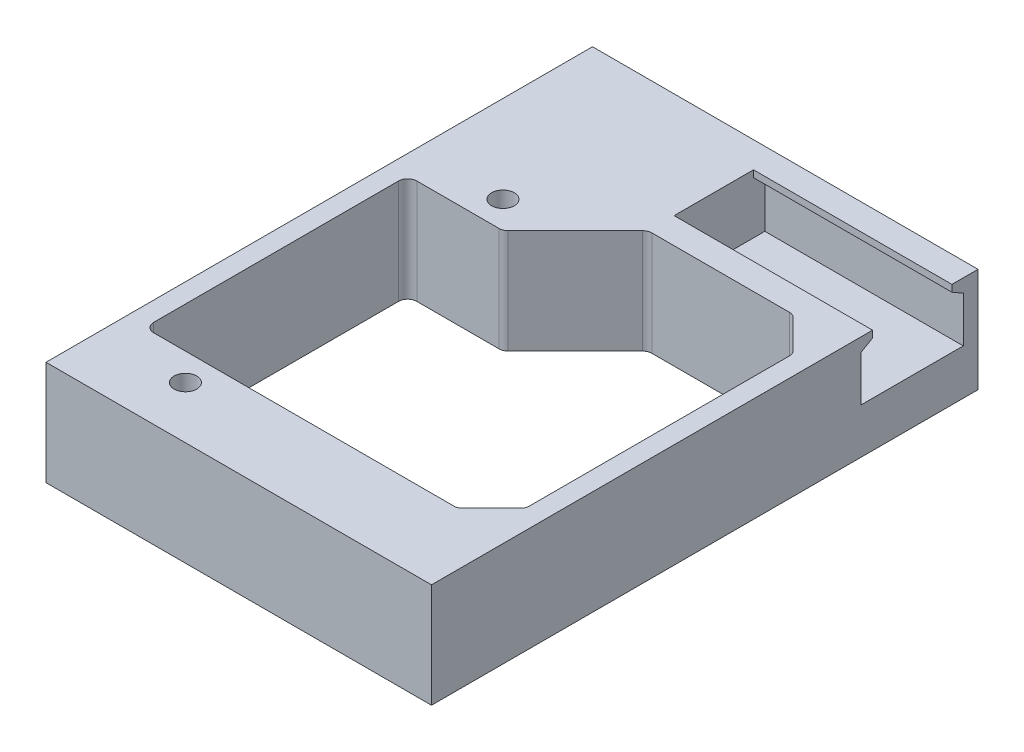
SolidWorks part; units mm, degrees
ref_plane "Front Plane" through (0, 0, 0) normal (0, 0, 1) x (1, 0, 0)
ref_plane "Top Plane" through (0, 0, 0) normal (0, 1, 0) x (1, 0, 0)
ref_plane "Right Plane" through (0, 0, 0) normal (1, 0, 0) x (0, 0, -1)
sketch "Sketch1" plane through (0, 0, 0) normal (0, 1, 0) x (1, 0, 0)
  line L0 (0, 0) -> (0, 59.6401) construction
  line L1 (-20, -19.2885) -> (-21.7, -19.2885)
  line L2 (20, 17.7115) -> (21.7, 17.7115)
  line L3 (20, 17.7115) -> (20, 69.9115)
  line L4 (20, 69.9115) -> (21.7, 69.9115)
  line L5 (21.7, 17.7115) -> (21.7, 69.9115)
  line L6 (20, 17.7115) -> (21.7, 17.7115)
  line L7 (20, 17.7115) -> (20, -19.2885)
  line L8 (20, -19.2885) -> (21.7, -19.2885)
  line L9 (21.7, 17.7115) -> (21.7, -19.2885)
  line L10 (-21.7, 17.7115) -> (-21.7, -19.2885)
  line L11 (-20, 17.7115) -> (-21.7, 17.7115)
  line L12 (-20, 17.7115) -> (-20, -19.2885)
  line L13 (-20, 69.9115) -> (-21.7, 69.9115)
  line L14 (-21.7, 17.7115) -> (-21.7, 69.9115)
  line L15 (-20, 17.7115) -> (-21.7, 17.7115)
  line L16 (-20, 17.7115) -> (-20, 69.9115)
  dimension "18" = 20
  dimension "D2" = 1.7
  dimension "D3" = 37
  dimension "D4" = 52.2
extrude "Boss-Extrude1" add sketch "Sketch1" against normal blind 9.2 from offset 1 contours L12 L11 L10 L1 | L11 L16 L13 L14 | L3 L2 L5 L4 offset against normal yes
sketch "Sketch4" plane through (0, -10.2, 0) normal (0, -1, 0) x (1, 0, 0)
  line L0 (-21.7, -69.9115) -> (-21.7, 19.2885) construction
  line L1 (12, -69.9115) -> (-21.7, -69.9115)
  line L2 (12, -69.9115) -> (12, -58.3115)
  line L3 (12, -58.3115) -> (-21.7, -58.3115)
  line L4 (-21.7, -69.9115) -> (-21.7, -58.3115)
  line L10 (-20, -69.9115) -> (-20, 19.2885) construction
  line L13 (-20, -69.9115) -> (-21.7, -69.9115) construction
  dimension "D1" = 11.6
  dimension "D2" = 32
extrude "Boss-Extrude3" add sketch "Sketch4" against normal up to surface (9.2 mm away)
sketch "Sketch3" plane through (0, -10.2, 0) normal (0, -1, 0) x (1, 0, 0)
  line L0 (-21.7, -69.9115) -> (-21.7, 19.2885) construction
  line L1 (-21.7, -58.9115) -> (-7.7, -58.9115)
  line L2 (-21.7, -58.9115) -> (-21.7, -51.9115)
  line L3 (-21.7, -51.9115) -> (-7.7, -51.9115)
  line L4 (-7.7, -58.9115) -> (-7.7, -51.9115)
  line L6 (0, 0) -> (0, -31.4212) construction
  line L13 (12, -69.9115) -> (-21.7, -69.9115) construction
  line L14 (-21.7, -40.3115) -> (-3.8096, -40.3115) construction
  line L15 (-21.7, -28.7115) -> (-7.7, -28.7115)
  line L16 (-7.7, -21.7115) -> (-7.7, -28.7115)
  line L17 (-21.7, -21.7115) -> (-7.7, -21.7115)
  line L18 (-21.7, -21.7115) -> (-21.7, -28.7115)
  line L19 (-20, -58.3115) -> (-20, 19.2885) construction
  circle A0 centre (-14, -54.3115) radius 1
  circle A2 centre (-14, -26.3115) radius 1
  dimension "D4" = 2.4
  dimension "D5" = 2
  dimension "D1" = 14
  dimension "D2" = 15.6
  dimension "D3" = 7
  dimension "D6" = 6
  dimension "D7" = 14
extrude "Servo Holder" add sketch "Sketch3" along normal blind 1 and the other way offset from surface (9.2 mm away) 1 other way up to plane "Top Plane"
sketch "Sketch37" plane through (0, -1, 0) normal (0, 1, 0) x (1, 0, 0)
  line L0 (-7.7, 21.7115) -> (-20, 21.7115) construction
  line L1 (12.3, 21.7115) -> (-7.7, 21.7115)
  line L2 (12.3, 21.7115) -> (12.3, 28.7115)
  line L3 (12.3, 28.7115) -> (-7.7, 28.7115)
  line L4 (-7.7, 21.7115) -> (-7.7, 28.7115)
  line L5 (-21.7, 69.9115) -> (-21.7, -19.2885) construction
  dimension "D1" = 34
extrude "Boss-Extrude19" add sketch "Sketch37" against normal up to surface (10.2 mm away) up to face at (-14.7, -11.2, -25.2115)
sketch "Sketch29" plane through (0, 0, -69.9115) normal (0, 0, -1) x (-1, 0, 0)
  line L1 (21.7, -10.2) -> (-12.7099, -10.2)
  line L2 (21.7, -10.2) -> (21.7, -16.1774)
  line L3 (21.7, -16.1774) -> (-12.7099, -16.1774)
  line L4 (-12.7099, -10.2) -> (-12.7099, -16.1774)
extrude "Cut-Extrude10" cut sketch "Sketch29" against normal through all both and the other way through all
sketch "Sketch30" plane through (0, 0, 0) normal (0, 0, 1) x (1, 0, 0)
  line L0 (-4.7, -1) -> (-4.7, -39) construction
  line L1 (12.3, -1) -> (-21.7, -1)
  line L2 (12.3, -1) -> (12.3, -39)
  line L3 (12.3, -39) -> (-21.7, -39)
  line L4 (-21.7, -1) -> (-21.7, -39)
  line L7 (-21.7, -1) -> (12.3, -1) construction
  line L9 (12.3, -1) -> (-20, -1) construction
  line L11 (-21.7, -10.2) -> (-21.7, -1) construction
  circle A0 centre (5.3, -34) radius 1.6
  circle A1 centre (5.3, -19) radius 1.6
  circle A2 centre (-14.7, -34) radius 1.6
  circle A3 centre (-14.7, -19) radius 1.6
  dimension "D2" = 10
  dimension "D4" = 15
  dimension "D1" = 17
  dimension "D3" = 38
  dimension "D5" = 18
  dimension "D6" = 10
extrude "Boss-Extrude13" add sketch "Sketch30" along normal blind 6.5 from offset 2 separate body
sketch "Sketch41" plane through (-20, 0, 0) normal (1, 0, 0) x (0, 0, -1)
  line L0 (21.7115, -1) -> (-19.2885, -1) construction
  line L1 (-2, -1) -> (-19.2885, -1)
  line L2 (-2, -1) -> (-2, -10.2)
  line L3 (-2, -10.2) -> (-19.2885, -10.2)
  line L4 (-19.2885, -1) -> (-19.2885, -10.2)
  line L5 (-2, -1) -> (-2, -39) construction
extrude "Cut-Extrude14" cut sketch "Sketch41" against normal blind 15
sketch "Sketch32" plane through (0, -39, 0) normal (0, -1, 0) x (1, 0, 0)
  line L1 (22.55, 8.5) -> (12.9564, 0.4867) construction
  line L2 (22.55, 8.5) -> (12.3, 8.5) construction
  line L4 (-21.7, 8.5) -> (12.3, 8.5) construction
  circle A0 centre (22.55, 8.5) radius 5
  circle A1 centre (22.55, 8.5) radius 12.5
  circle A2 centre (15.2588, 2.4099) radius 1.45
  circle A3 centre (16.4599, 15.7912) radius 1.45
  circle A4 centre (29.8412, 14.5901) radius 1.45
  circle A5 centre (28.6401, 1.2088) radius 1.45
  point P18 (22.55, 8.5)
  line M1 (-21.7, 2) -> (12.3, 2)
  line M2 (12.3, 2) -> (12.3, 8.5)
  line M3 (12.3, 8.5) -> (-21.7, 8.5)
  dimension "D1" = 9.5
  dimension "D2" = 25
  dimension "D4" = 10
  dimension "D5" = 10.25
  dimension "D3" = 4
extrude "Boss-Extrude14" add sketch "Sketch32" along normal blind 8.8 from surface at -38 contours A1 A5 A4 A3 A2 A0 M1 M3 M2 starting at face at (-3.85, -1, 5.25)
sketch "Sketch34" plane through (-21.7, 0, 0) normal (-1, 0, 0) x (0, 0, 1)
  line L1 (-21.7115, -1) -> (-21.7115, -9.8)
  line L5 (-69.9115, -1) -> (2, -1) construction
  line L7 (-21.7115, -9.8) -> (2, -39)
  line L8 (-21.7115, -10.2) -> (-21.7115, -1) construction
  line L9 (2, -39) -> (8.5, -39)
  line L10 (8.5, -39) -> (8.5, -1)
  line L11 (8.5, -1) -> (-21.7115, -1)
extrude "Boss-Extrude16" add sketch "Sketch34" against normal blind 3
sketch "Sketch35" plane through (12.3, 0, 0) normal (1, 0, 0) x (0, 0, -1)
  line L0 (-2, -1) -> (21.7115, -1)
  line L1 (21.7115, -1) -> (21.7115, -9.8)
  line L3 (-8.5, -9.8) -> (-8.5, -1)
  line L4 (-8.5, -1) -> (-2, -1)
  line L5 (21.7115, -10.2) -> (21.7115, -1) construction
  line L8 (-8.5, -39) -> (-8.5, -9.8) construction
  line L9 (21.7115, -1) -> (28.7115, -1) construction
  line L10 (21.7115, -9.8) -> (-2, -39)
  line L11 (-2, -39) -> (-8.5, -39)
  line L12 (-8.5, -39) -> (-8.5, -9.8)
extrude "Boss-Extrude17" add sketch "Sketch35" against normal blind 3
sketch "Sketch36" plane through (0, -10.2, 0) normal (0, -1, 0) x (1, 0, 0)
  line L0 (12.3, -10.5792) -> (16.6342, -2.5115)
  line L2 (16.6342, -2.5115) -> (12.3, 1.3455)
  line L3 (12.3, 1.3455) -> (12.3, -10.5792)
  line L4 (22.55, 8.5) -> (12.3, -10.5792) construction
  line L5 (12.3, 8.5) -> (12.3, 2) construction
  arc A1 (12.3, 1.3455) -> (10.05, 8.5) centre (22.55, 8.5) ccw construction
extrude "Boss-Extrude18" add sketch "Sketch36" against normal up to surface (9.2 mm away)
fillet "Fillet9" [suppressed] radius 1
sketch "Sketch39" plane through (0, -1, 0) normal (0, 1, 0) x (1, 0, 0)
  line L0 (-21.7, 69.9115) -> (12, 69.9115) construction
  line L1 (12.3, 28.7115) -> (10.6, 28.7115)
  line L2 (12.3, 28.7115) -> (12.3, 69.9115)
  line L3 (12.3, 69.9115) -> (10.6, 69.9115)
  line L4 (10.6, 28.7115) -> (10.6, 69.9115)
  line L5 (-20, 28.7115) -> (12.3, 28.7115) construction
  line L6 (12.3, 10.5792) -> (12.3, 28.7115) construction
  point P7 (12.3, 49.3115)
  dimension "D1" = 1.7
extrude "Boss-Extrude20" add sketch "Sketch39" against normal up to surface (9.2 mm away) up to face at (-7.5167, -10.2, -41.9907)
sketch "Sketch40" plane through (12.3, 0, 0) normal (1, 0, 0) x (0, 0, -1)
  line L1 (60.6115, -1) -> (67.6115, -1)
  line L6 (60.6115, -2.2) -> (59.6115, -2.2)
  line L7 (59.6115, -2.2) -> (59.6115, -6.2)
  line L8 (59.6115, -6.2) -> (68.6115, -6.2)
  line L9 (64.1115, -6.2) -> (64.1115, -1)
  line L11 (68.6115, -2.2) -> (68.6115, -6.2)
  line L12 (67.6115, -2.2) -> (68.6115, -2.2)
  line L13 (67.6115, -1) -> (67.6115, -2.2)
  line L14 (69.9115, -10.2) -> (69.9115, -1) construction
  line L15 (60.6115, -2.2) -> (60.6115, -1)
  line L16 (10.5792, -1) -> (69.9115, -1) construction
  point P9 (59.6115, -4.2)
  dimension "D1" = 5.8
  dimension "D2" = 3.5
  dimension "D3" = 4.5
  dimension "D4" = 4
  dimension "D5" = 1.2
  dimension "D6" = 3.5
  dimension "D7" = 1
extrude "Cut-Extrude13" cut sketch "Sketch40" against normal blind 17.5
chamfer "Chamfer2" distance 0.6 angle 60 2 edges at (3.55, -2.2, -67.6115) (3.55, -2.2, -60.6115)
chamfer "Chamfer3" distance 3 angle 45 2 edges at (10.6, -5.6, -28.7115) (10.6, -5.6, -58.3115)
fillet "Fillet10" radius 6 2 edges at (16.6342, -5.4, -2.5115) (12.3, -5.6, -10.5792)
sketch "Sketch42" plane through (0, 0, 8.5) normal (0, 0, 1) x (1, 0, 0)
  line L0 (-4.7, -39) -> (-4.7, -1) construction
  line L3 (-21.7, -39) -> (12.3, -39) construction
  line L4 (10.05, -1) -> (-21.7, -1) construction
  line L5 (-1.1, -1) -> (-1.1, -10.6)
  line L6 (-8.3, -1) -> (-8.3, -10.6)
  line L7 (-1.1, -1) -> (-8.3, -1)
  arc A0 (-1.1, -10.6) -> (-8.3, -10.6) centre (-4.7, -10.6) cw
  point P11 (-4.7, -14.2)
  dimension "D1" = 3.6
  dimension "D2" = 13.2
extrude "Cut-Extrude15" cut sketch "Sketch42" against normal blind 10
chamfer "Chamfer4" distance 2.5 angle 45 1 edges at (-7.7, -5.6, -58.3115)
sketch "Sketch43" plane through (0, -1, 0) normal (0, 1, 0) x (1, 0, 0)
  line L0 (-5.2, 58.3115) -> (-11.6, 51.9115)
  line L1 (-7.7, 51.9115) -> (-20, 51.9115) construction
  line L2 (-11.6, 51.9115) -> (-5.2, 51.9115)
  line L3 (-5.2, 51.9115) -> (-5.2, 58.3115)
extrude "Cut-Extrude16" cut sketch "Sketch43" against normal blind 10
fillet "Fillet11" radius 0.8 8 edges at (-20, -5.6, -51.9115) (-20, -5.6, -28.7115) (7.6, -5.6, -28.7115) (10.6, -5.6, -31.7115) (10.6, -5.6, -55.3115) (7.6, -5.6, -58.3115) (-11.6, -5.6, -51.9115) (-5.2, -5.6, -58.3115)
sketch "Sketch44" plane through (0, -1, 0) normal (0, 1, 0) x (1, 0, 0)
  line L1 (37.4929, 21.7115) -> (-21.7, 21.7115)
  line L2 (37.4929, 21.7115) -> (37.4929, -23.7056)
  line L3 (37.4929, -23.7056) -> (-21.7, -23.7056)
  line L4 (-21.7, 21.7115) -> (-21.7, -23.7056)
  point P6 (0, 0)
extrude "Cut-Extrude17" cut sketch "Sketch44" against normal through all
